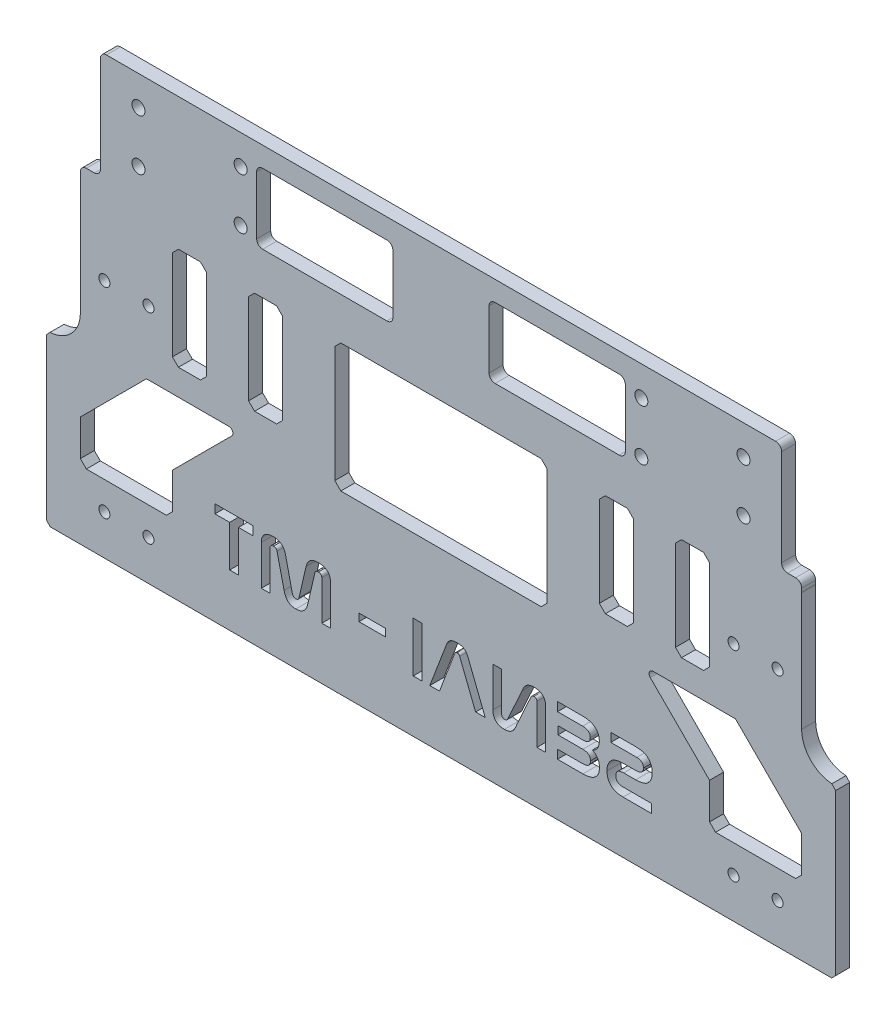
SolidWorks part; units mm, degrees
material "Liga 1060"
ref_plane "Plano frontal" through (0, 0, 0) normal (0, 0, 1) x (1, 0, 0)
ref_plane "Plano superior" through (0, 0, 0) normal (0, 1, 0) x (1, 0, 0)
ref_plane "Plano direito" through (0, 0, 0) normal (1, 0, 0) x (0, 0, -1)
sketch "Esboço1" plane through (0, 0, 0) normal (0, 0, 1) x (1, 0, 0)
  line L30 (-10, 125) -> (-10, 173)
  line L31 (-13, 176) -> (-347, 176)
  line L32 (-350, 173) -> (-350, 125)
  line L33 (-353, 122) -> (-357, 122)
  line L34 (-360, 119) -> (-360, 58)
  line L35 (-375.1111, 42.0247) -> (-377, 40.0278)
  line L36 (-377, 40.0278) -> (-377, -40)
  line L37 (-377, -40) -> (-375, -42)
  line L38 (-375, -42) -> (15, -42)
  line L39 (15, -42) -> (17, -40)
  line L40 (17, -40) -> (17, 40.0278)
  line L41 (17, 40.0278) -> (15.1111, 42.0247)
  line L42 (0, 58) -> (0, 117)
  line L43 (0, 117.2828) -> (0, 119)
  line L44 (-3, 122) -> (-7, 122)
  arc A20 (-10, 173) -> (-13, 176) centre (-13, 173) ccw
  arc A21 (-347, 176) -> (-350, 173) centre (-347, 173) ccw
  arc A22 (-353, 122) -> (-350, 125) centre (-353, 125) ccw
  arc A23 (-357, 122) -> (-360, 119) centre (-357, 119) ccw
  arc A24 (-375.1111, 42.0247) -> (-360, 58) centre (-376, 58) ccw
  arc A25 (0, 58) -> (15.1111, 42.0247) centre (16, 58) ccw
  arc A26 (0, 117) -> (-0.0295, 117.4199) centre (-3, 117) ccw
  arc A27 (0, 117.2828) -> (-0.0295, 117.4199) centre (-3.3115, 116.6414) ccw
  arc A28 (0, 119) -> (-3, 122) centre (-3, 119) ccw
  arc A29 (-10, 125) -> (-7, 122) centre (-7, 125) ccw
extrude "Ressalto-extrusão1" add sketch "Esboço1" along normal blind 6 contours L31 A21 L32 A22 L33 A23 L34 A24 L35 L36 L37 L38 L39 L40 L41 A25 L42 A26 A27 L43 A28 L44 A29 L30 A20
sketch "Esboço2" plane through (0, 0, 6) normal (0, 0, 1) x (1, 0, 0)
  line L0 (-180, 176) -> (-180, -42) construction
  line L1 (-13, 176) -> (-347, 176) construction
  line L2 (-375, -42) -> (15, -42) construction
  line L3 (-350, 173) -> (-350, 125) construction
  line L4 (-272, 166) -> (-204, 166)
  line L5 (-272, 166) -> (-272, 131)
  line L6 (-272, 131) -> (-204, 131)
  line L7 (-204, 166) -> (-204, 131)
  line L8 (-331, 161.2) -> (-280, 161.2) construction
  line L9 (-331, 161.2) -> (-331, 135.8) construction
  line L10 (-331, 135.8) -> (-280, 135.8) construction
  line L11 (-280, 161.2) -> (-280, 135.8) construction
  line L12 (-280, 148.5) -> (-272, 148.5) construction
  line L13 (-80, 148.5) -> (-88, 148.5) construction
  line L14 (-80, 161.2) -> (-80, 135.8) construction
  line L15 (-29, 135.8) -> (-80, 135.8) construction
  line L16 (-29, 161.2) -> (-29, 135.8) construction
  line L17 (-29, 161.2) -> (-80, 161.2) construction
  line L18 (-156, 166) -> (-156, 131)
  line L19 (-88, 131) -> (-156, 131)
  line L20 (-88, 166) -> (-88, 131)
  line L21 (-88, 166) -> (-156, 166)
  circle A0 centre (-331, 161.2) radius 3.25
  circle A1 centre (-280, 161.2) radius 3.25
  circle A2 centre (-331, 135.8) radius 3.25
  circle A3 centre (-280, 135.8) radius 3.25
  circle A4 centre (-80, 135.8) radius 3.25
  circle A5 centre (-29, 135.8) radius 3.25
  circle A6 centre (-80, 161.2) radius 3.25
  circle A7 centre (-29, 161.2) radius 3.25
  dimension "D3" = 25.4
  dimension "D5" = 6.5
  dimension "D1" = 51
  dimension "D2" = 68
  dimension "D4" = 35
  dimension "D6" = 8
  dimension "D7" = 10
  dimension "D8" = 78
extrude "Corte-extrusão1" cut sketch "Esboço2" against normal blind 6
fillet "Filete1" radius 3 8 edges at (-88, 131, 3) (-88, 166, 3) (-156, 166, 3) (-156, 131, 3) (-272, 131, 3) (-204, 131, 3) (-204, 166, 3) (-272, 166, 3)
sketch "Esboço3" plane through (0, 0, 0) normal (0, 0, -1) x (-1, 0, 0)
  line L0 (375, -42) -> (-15, -42) construction
  line L1 (12, 78) -> (34, 78) construction
  line L2 (12, 78) -> (12, -22) construction
  line L3 (12, -22) -> (34, -22) construction
  line L4 (34, 78) -> (34, -22) construction
  line L5 (180, 176) -> (180, -42) construction
  line L6 (13, 176) -> (347, 176) construction
  line L7 (326, 78) -> (326, -22) construction
  line L8 (348, -22) -> (326, -22) construction
  line L9 (348, 78) -> (348, -22) construction
  line L10 (348, 78) -> (326, 78) construction
  circle A0 centre (12, 78) radius 2.75
  circle A1 centre (34, 78) radius 2.75
  circle A2 centre (12, -22) radius 2.75
  circle A3 centre (34, -22) radius 2.75
  circle A4 centre (326, -22) radius 2.75
  circle A5 centre (348, -22) radius 2.75
  circle A6 centre (326, 78) radius 2.75
  circle A7 centre (348, 78) radius 2.75
  dimension "D5" = 5.5
  dimension "D6" = 5.5
  dimension "D1" = 22
  dimension "D2" = 100
  dimension "D3" = 20
  dimension "D4" = 146
extrude "Corte-extrusão2" cut sketch "Esboço3" against normal through all
sketch "Esboço4" plane through (0, 0, 0) normal (0, 0, -1) x (-1, 0, 0)
  line L8 (127, 110) -> (233, 110)
  line L9 (127, 110) -> (127, 46)
  line L10 (233, 110) -> (233, 46)
  line L11 (127, 46) -> (233, 46)
  line L26 (180, 110) -> (180, 176) construction
  line L27 (13, 176) -> (347, 176) construction
  line L28 (153, 131) -> (91, 131) construction
  dimension "D1" = 21
  dimension "D2" = 106
  dimension "D3" = 64
extrude "Corte-extrusão3" cut sketch "Esboço4" against normal through all
sketch "Esboço6" plane through (0, 0, 6) normal (0, 0, 1) x (1, 0, 0)
  text T0 " canintech" font "Neuropolitical Rg" height 26
extrude "Corte-extrusão4" cut sketch "Esboço6" against normal through all
sketch "Esboço7" plane through (0, 0, 6) normal (0, 0, 1) x (1, 0, 0)
  line L10 (-248.1953, 1.4651) -> (-242.6122, 1.4651)
  line L11 (-242.6137, 0.1618) -> (-242.6082, 5.1384) construction
  line L12 (-252.0392, -3.858) -> (-243.1564, -3.858)
  line L13 (-252.0392, -3.858) -> (-252.0392, 1.4637)
  line L14 (-262.9825, 1.4596) -> (-248.1953, 1.4651) construction
  line L15 (-252.0392, 1.4637) -> (-248.1953, 1.4651)
  line L16 (-242.6122, 1.4651) -> (-242.6122, -3.858)
  line L17 (-242.6122, -3.858) -> (-243.1564, -3.858)
  spline S0 degree 3 poles (-251.9587, -7.6854) (-251.529, -7.6843) (-250.7044, -7.6821) (-249.5179, -7.6097) (-248.4335, -7.4883) (-247.4508, -7.3043) (-246.5724, -7.0585) (-245.7969, -6.7579) (-245.1214, -6.4027) (-244.5487, -5.9757) (-244.0577, -5.483) (-243.6518, -4.9061) (-243.3004, -4.2586) (-243.0287, -3.5244) (-242.8221, -2.7132) (-242.68, -1.8243) (-242.6116, -0.8566) (-242.613, -0.1865) (-242.6137, 0.1618) knots 0 0 0 0 0.089644 0.172025 0.247884 0.317196 0.380397 0.437928 0.490462 0.539112 0.586442 0.63495 0.685774 0.739761 0.797833 0.860209 0.927326 1 1 1 1 construction
extrude "Ressalto-extrusão3" add sketch "Esboço7" against normal through all
chamfer "Chanfro1" distance 3 angle 45 4 edges at (-233, 110, 3) (-127, 110, 3) (-127, 46, 3) (-233, 46, 3)
sketch "Esboço8" plane through (0, 0, 6) normal (0, 0, 1) x (1, 0, 0)
  line L0 (-123.9584, 4.2367) -> (-123.9584, 0.7613)
  line L1 (-139.488, 0.7613) -> (-118.3713, 0.7613) construction
  line L2 (-123.9584, 0.7613) -> (-139.488, 0.7613)
  line L3 (-139.488, 0.7613) -> (-139.488, 4.2367)
  line L4 (-139.488, 4.2367) -> (-123.9584, 4.2367)
extrude "Ressalto-extrusão4" add sketch "Esboço8" against normal through all
sketch "Esboço9" plane through (0, 0, 6) normal (0, 0, 1) x (1, 0, 0)
  line L0 (-123.9584, 0.7613) -> (-123.9584, 4.2367)
  line L1 (-123.9584, 0.7613) -> (-128.9584, 0.7613)
  line L2 (-123.9584, 4.2367) -> (-128.9584, 4.2367)
  line L3 (-128.9584, 0.7613) -> (-128.9584, 4.2367)
  dimension "D1" = 5
extrude "Corte-extrusão5" cut sketch "Esboço9" against normal through all
sketch "Esboço10" plane through (0, 0, 6) normal (0, 0, 1) x (1, 0, 0)
  line L0 (-360, 13) -> (-360, -8)
  line L1 (-360, -8) -> (-314.0427, -8)
  line L2 (-314.0427, -8) -> (-314.0427, 13)
  line L3 (-281.0427, 46) -> (-259.0427, 46)
  line L4 (-259.0427, 46) -> (-259.0427, 110)
  line L5 (-259.0427, 110) -> (-314.0427, 110)
  line L6 (-314.0427, 110) -> (-314.0427, 58.9573)
  line L7 (-360, 13) -> (-314.0427, 58.9573)
  line L8 (-360, 119) -> (-360, 58) construction
  line L9 (-233, 49) -> (-233, 107) construction
  line L10 (-314.0427, 13) -> (-281.0427, 46)
  line L11 (-230, 110) -> (-130, 110) construction
  line L12 (-130, 46) -> (-230, 46) construction
  line L16 (-375, -42) -> (15, -42) construction
  line L17 (-180, 110) -> (-180, 46) construction
  line L18 (-45.9573, -8) -> (-45.9573, 13)
  line L19 (0, -8) -> (-45.9573, -8)
  line L20 (0, 13) -> (0, -8)
  line L21 (0, 13) -> (-45.9573, 58.9573)
  line L22 (-45.9573, 110) -> (-45.9573, 58.9573)
  line L23 (-100.9573, 110) -> (-45.9573, 110)
  line L24 (-100.9573, 46) -> (-100.9573, 110)
  line L25 (-78.9573, 46) -> (-100.9573, 46)
  line L26 (-45.9573, 13) -> (-78.9573, 46)
  dimension "D1" = 26.0427
  dimension "D2" = 55
  dimension "D3" = 135
  dimension "D4" = 34
  dimension "D5" = 21
  dimension "D6" = 21
extrude "Corte-extrusão6" cut sketch "Esboço10" against normal through all
sketch "Esboço11" plane through (0, 0, 6) normal (0, 0, 1) x (1, 0, 0)
  line L0 (-281.0427, 46) -> (-327, 46)
  line L1 (-314.0427, 58.9573) -> (-360, 13) construction
  line L2 (-314.0427, 58.9573) -> (-327, 46)
  line L3 (-314.0427, 58.9573) -> (-259.0427, 58.9573)
  line L4 (-259.0427, 46) -> (-259.0427, 110) construction
  line L5 (-259.0427, 58.9573) -> (-259.0427, 46)
  line L6 (-259.0427, 46) -> (-281.0427, 46)
  line L7 (-100.9573, 46) -> (-33, 46)
  line L8 (0, 13) -> (-45.9573, 58.9573) construction
  line L9 (-33, 46) -> (-45.9573, 58.9573)
  line L10 (-45.9573, 58.9573) -> (-100.9573, 58.9573)
  line L11 (-100.9573, 110) -> (-100.9573, 46) construction
  line L12 (-100.9573, 58.9573) -> (-100.9573, 46)
extrude "Ressalto-extrusão5" add sketch "Esboço11" against normal through all contours L10 L12 L7 L9 | L6 L0 L2 L3 L5
sketch "Esboço12" plane through (0, 0, 6) normal (0, 0, 1) x (1, 0, 0)
  line L0 (-297.0427, 110) -> (-297.0427, 58.9573)
  line L1 (-297.0427, 110) -> (-276.0427, 110)
  line L2 (-297.0427, 58.9573) -> (-276.0427, 58.9573)
  line L3 (-276.0427, 110) -> (-276.0427, 58.9573)
  line L4 (-259.0427, 110) -> (-314.0427, 110) construction
  line L5 (-314.0427, 58.9573) -> (-259.0427, 58.9573) construction
  line L6 (-62.9573, 110) -> (-62.9573, 58.9573)
  line L7 (-62.9573, 110) -> (-83.9573, 110)
  line L8 (-62.9573, 58.9573) -> (-83.9573, 58.9573)
  line L9 (-83.9573, 110) -> (-83.9573, 58.9573)
  line L10 (-45.9573, 110) -> (-100.9573, 110) construction
  line L11 (-45.9573, 58.9573) -> (-100.9573, 58.9573) construction
  line L13 (-276.0427, 110) -> (-259.0427, 110) construction
  line L14 (-297.0427, 110) -> (-314.0427, 110) construction
  line L15 (-83.9573, 110) -> (-100.9573, 110) construction
  line L16 (-62.9573, 110) -> (-45.9573, 110) construction
  dimension "D1" = 21
  dimension "D2" = 21
extrude "Ressalto-extrusão6" add sketch "Esboço12" against normal through all
chamfer "Chanfro3" distance 3 angle 45 20 edges at (0, -8, 3) (-45.9573, -8, 3) (-314.0427, -8, 3) (-360, -8, 3) (-62.9573, 58.9573, 2.9927) (-45.9573, 58.9573, 3) (-83.9573, 58.9573, 2.9927) (-100.9573, 58.9573, 3) (-62.9573, 110, 3) (-100.9573, 110, 3) (-83.9573, 110, 3) (-45.9573, 110, 3) (-259.0427, 110, 3) (-297.0427, 110, 3) (-314.0427, 110, 3) (-276.0427, 110, 3) (-259.0427, 58.9573, 3) (-297.0427, 58.9573, 2.9927) (-276.0427, 58.9573, 2.9927) (-314.0427, 58.9573, 3)
sketch "Esboço13" plane through (0, 0, 6) normal (0, 0, 1) x (1, 0, 0)
  text T0 "SENAI MT - SINOP - BRASIL" font "Neuropolitical Rg" height 10
extrude "Corte-extrusão7" cut sketch "Esboço13" against normal through all
sketch "Esboço14" plane through (0, 0, 6) normal (0, 0, 1) x (1, 0, 0)
  line L0 (-258.8839, -26.4965) -> (-259.9219, -28.2139)
  line L1 (-259.9219, -28.2139) -> (-253.0215, -28.2139)
  line L2 (-253.0215, -28.2139) -> (-254.0594, -26.4965)
  line L3 (-254.0594, -26.4965) -> (-258.8839, -26.4965)
  line L25 (-147.8817, -25.9424) -> (-147.8817, -27.6852)
  line L26 (-147.8817, -25.9424) -> (-144.8817, -25.9424)
  line L29 (-147.8817, -27.6852) -> (-144.8817, -27.6852)
  line L65 (-144.8817, -25.9424) -> (-144.8817, -27.6852)
  line L68 (-158.9663, -22.3954) -> (-158.9663, -20.4568)
  line L70 (-158.9663, -22.3954) -> (-158.9663, -22.5502)
  line L71 (-158.9663, -22.5502) -> (-155.9663, -22.5502)
  line L72 (-155.9663, -22.3954) -> (-155.9663, -22.5502)
  line L73 (-158.9663, -20.4568) -> (-155.9663, -20.4568)
  line L74 (-155.9663, -20.4568) -> (-155.9663, -22.5502)
  line L75 (-88.867, -26.4965) -> (-84.0425, -26.4965)
  line L76 (-158.9663, -28.1647) -> (-155.9663, -28.1647)
  line L77 (-158.9663, -28.1647) -> (-158.9663, -31.247)
  line L78 (-158.9663, -31.247) -> (-155.9663, -31.247)
  line L79 (-155.9663, -28.1647) -> (-155.9663, -31.247)
  line L80 (-84.0425, -26.4965) -> (-83.0045, -28.2139)
  line L81 (-83.0045, -28.2139) -> (-89.905, -28.2139)
  line L82 (-89.905, -28.2139) -> (-88.867, -26.4965)
  line L83 (-98.7298, -25.5363) -> (-104.2945, -25.5363) construction
  line L84 (-98.4573, -25.5363) -> (-104.2945, -25.5363)
  line L85 (-98.4573, -25.5363) -> (-98.4573, -27.1437)
  line L86 (-98.4573, -27.1437) -> (-104.2945, -27.1437)
  line L87 (-104.2945, -25.5363) -> (-104.2945, -27.1437)
  line L88 (-104.2945, -30.5278) -> (-104.2945, -26.9061) construction
  line L89 (-100.3996, -27.1437) -> (-98.6088, -27.1437) construction
  line L90 (-111.1748, -20.5405) -> (-119.5737, -20.5385) construction
  line L91 (-115.3743, -20.5395) -> (-112.6341, -20.5395)
  line L92 (-115.3743, -20.5395) -> (-115.3743, -22.3952)
  line L93 (-115.3743, -22.3952) -> (-112.6341, -22.3952)
  line L94 (-112.6341, -20.5395) -> (-112.6341, -22.3952)
  line L95 (-117.4248, -22.3952) -> (-111.3517, -22.3952) construction
  line L96 (-111.1452, -28.6623) -> (-117.4248, -28.6604) construction
  line L97 (-115.3002, -28.661) -> (-112.6341, -28.661)
  line L98 (-115.3002, -28.661) -> (-115.3002, -30.5171)
  line L99 (-115.3002, -30.5171) -> (-112.6341, -30.5171)
  line L100 (-112.6341, -28.661) -> (-112.6341, -30.5171)
  line L101 (-119.5737, -30.5171) -> (-111.0266, -30.5171) construction
  dimension "D1" = 3
  dimension "D2" = 3
extrude "Ressalto-extrusão8" add sketch "Esboço14" against normal through all
fillet "Filete2" radius 2 2 edges at (-281.0427, 46, 3) (-78.9573, 46, 3)
sketch "Esboço15" plane through (0, 0, 6) normal (0, 0, 1) x (1, 0, 0)
  line L0 (-305.1197, 14.02) -> (-201.8576, 26.6471)
  line L1 (-201.8576, 26.6471) -> (-69.1323, 24.9635)
  line L2 (-69.1323, 24.9635) -> (-54.2603, 12.0557)
  line L3 (-54.2603, 12.0557) -> (-48.46, -35.3775)
  line L4 (-48.46, -35.3775) -> (-307.6451, -35.3775)
  line L5 (-307.6451, -35.3775) -> (-305.1197, 14.02)
extrude "Ressalto-extrusão9" add sketch "Esboço15" against normal through all contours L5 L4 L3 L2 L1 L0
sketch "Esboço16" plane through (0, 0, 0) normal (0, 0, 1) x (1, 0, 0)
  line L15 (-13, 176) -> (-347, 176)
  line L16 (-350, 173) -> (-350, 125)
  line L17 (-353, 122) -> (-357, 122)
  line L18 (-360, 119) -> (-360, 58)
  line L19 (-375.1111, 42.0247) -> (-377, 40.0278)
  line L20 (-377, 40.0278) -> (-377, -40)
  line L21 (-377, -40) -> (-375, -42)
  line L22 (-375, -42) -> (15, -42)
  line L23 (15, -42) -> (17, -40)
  line L24 (17, -40) -> (17, 40.0278)
  line L25 (17, 40.0278) -> (15.1111, 42.0247)
  line L26 (0, 58) -> (0, 117)
  line L27 (0, 117.2828) -> (0, 119)
  line L28 (-3, 122) -> (-7, 122)
  line L29 (-10, 125) -> (-10, 173)
  line L30 (-13, 176) -> (-347, 176)
  line L31 (-350, 173) -> (-350, 125)
  line L32 (-353, 122) -> (-357, 122)
  line L33 (-360, 119) -> (-360, 58)
  line L34 (-375.1111, 42.0247) -> (-377, 40.0278)
  line L35 (-377, 40.0278) -> (-377, -40)
  line L36 (-377, -40) -> (-375, -42)
  line L37 (-375, -42) -> (15, -42)
  line L38 (15, -42) -> (17, -40)
  line L39 (17, -40) -> (17, 40.0278)
  line L40 (17, 40.0278) -> (15.1111, 42.0247)
  line L41 (0, 58) -> (0, 117)
  line L42 (0, 117.2828) -> (0, 119)
  line L43 (-3, 122) -> (-7, 122)
  line L44 (-10, 125) -> (-10, 173)
  arc A10 (-10, 173) -> (-13, 176) centre (-13, 173) ccw
  arc A11 (-347, 176) -> (-350, 173) centre (-347, 173) ccw
  arc A12 (-353, 122) -> (-350, 125) centre (-353, 125) ccw
  arc A13 (-357, 122) -> (-360, 119) centre (-357, 119) ccw
  arc A14 (-375.1111, 42.0247) -> (-360, 58) centre (-376, 58) ccw
  arc A15 (0, 58) -> (15.1111, 42.0247) centre (16, 58) ccw
  arc A16 (0, 117) -> (-0.0295, 117.4199) centre (-3, 117) ccw
  arc A17 (0, 117.2828) -> (-0.0295, 117.4199) centre (-3.3115, 116.6414) ccw
  arc A18 (0, 119) -> (-3, 122) centre (-3, 119) ccw
  arc A19 (-10, 125) -> (-7, 122) centre (-7, 125) ccw
  arc A20 (-10, 173) -> (-13, 176) centre (-13, 173) ccw
  arc A21 (-347, 176) -> (-350, 173) centre (-347, 173) ccw
  arc A22 (-353, 122) -> (-350, 125) centre (-353, 125) ccw
  arc A23 (-357, 122) -> (-360, 119) centre (-357, 119) ccw
  arc A24 (-375.1111, 42.0247) -> (-360, 58) centre (-376, 58) ccw
  arc A25 (0, 58) -> (15.1111, 42.0247) centre (16, 58) ccw
  arc A26 (0, 117) -> (-0.0295, 117.4199) centre (-3, 117) ccw
  arc A27 (0, 117.2828) -> (-0.0295, 117.4199) centre (-3.3115, 116.6414) ccw
  arc A28 (0, 119) -> (-3, 122) centre (-3, 119) ccw
  arc A29 (-10, 125) -> (-7, 122) centre (-7, 125) ccw
  dimension "D1" = 0
extrude "Ressalto-extrusão10" add sketch "Esboço16" against normal blind 1
sketch "Esboço17" plane through (0, 0, 0) normal (0, 0, 1) x (1, 0, 0)
  line L0 (0, 13) -> (-33, 46) construction
  line L1 (-33, 46) -> (-74.1288, 46) construction
  line L2 (-75.5431, 42.5858) -> (-45.9573, 13) construction
  line L3 (-45.9573, 13) -> (-45.9573, -5) construction
  line L4 (-45.9573, -5) -> (-42.9573, -8) construction
  line L5 (-42.9573, -8) -> (-3, -8) construction
  line L6 (-3, -8) -> (0, -5) construction
  line L7 (0, -5) -> (0, 13) construction
  line L8 (-285.8712, 46) -> (-327, 46) construction
  line L9 (-327, 46) -> (-360, 13) construction
  line L10 (-360, 13) -> (-360, -5) construction
  line L11 (-360, -5) -> (-357, -8) construction
  line L12 (-357, -8) -> (-317.0427, -8) construction
  line L13 (-317.0427, -8) -> (-314.0427, -5) construction
  line L14 (-314.0427, -5) -> (-314.0427, 13) construction
  line L15 (-314.0427, 13) -> (-284.4569, 42.5858) construction
  line L16 (-273.0427, 58.9573) -> (-262.0427, 58.9573) construction
  line L17 (-262.0427, 58.9573) -> (-259.0427, 61.9573) construction
  line L18 (-259.0427, 61.9573) -> (-259.0427, 107) construction
  line L19 (-259.0427, 107) -> (-262.0427, 110) construction
  line L20 (-262.0427, 110) -> (-273.0427, 110) construction
  line L21 (-273.0427, 110) -> (-276.0427, 107) construction
  line L22 (-276.0427, 107) -> (-276.0427, 61.9573) construction
  line L23 (-276.0427, 61.9573) -> (-273.0427, 58.9573) construction
  line L24 (-311.0427, 58.9573) -> (-300.0427, 58.9573) construction
  line L25 (-300.0427, 58.9573) -> (-297.0427, 61.9573) construction
  line L26 (-297.0427, 61.9573) -> (-297.0427, 107) construction
  line L27 (-297.0427, 107) -> (-300.0427, 110) construction
  line L28 (-300.0427, 110) -> (-311.0427, 110) construction
  line L29 (-311.0427, 110) -> (-314.0427, 107) construction
  line L30 (-314.0427, 107) -> (-314.0427, 61.9573) construction
  line L31 (-314.0427, 61.9573) -> (-311.0427, 58.9573) construction
  line L32 (-127, 107) -> (-130, 110) construction
  line L33 (-130, 110) -> (-230, 110) construction
  line L34 (-230, 110) -> (-233, 107) construction
  line L35 (-233, 107) -> (-233, 49) construction
  line L36 (-233, 49) -> (-230, 46) construction
  line L37 (-230, 46) -> (-130, 46) construction
  line L38 (-130, 46) -> (-127, 49) construction
  line L39 (-127, 49) -> (-127, 107) construction
  line L40 (-100.9573, 61.9573) -> (-97.9573, 58.9573) construction
  line L41 (-97.9573, 58.9573) -> (-86.9573, 58.9573) construction
  line L42 (-86.9573, 58.9573) -> (-83.9573, 61.9573) construction
  line L43 (-83.9573, 61.9573) -> (-83.9573, 107) construction
  line L44 (-83.9573, 107) -> (-86.9573, 110) construction
  line L45 (-86.9573, 110) -> (-97.9573, 110) construction
  line L46 (-97.9573, 110) -> (-100.9573, 107) construction
  line L47 (-100.9573, 107) -> (-100.9573, 61.9573) construction
  line L48 (-62.9573, 61.9573) -> (-59.9573, 58.9573) construction
  line L49 (-59.9573, 58.9573) -> (-48.9573, 58.9573) construction
  line L50 (-48.9573, 58.9573) -> (-45.9573, 61.9573) construction
  line L51 (-45.9573, 61.9573) -> (-45.9573, 107) construction
  line L52 (-45.9573, 107) -> (-48.9573, 110) construction
  line L53 (-48.9573, 110) -> (-59.9573, 110) construction
  line L54 (-59.9573, 110) -> (-62.9573, 107) construction
  line L55 (-62.9573, 107) -> (-62.9573, 61.9573) construction
  line L56 (-91, 166) -> (-153, 166) construction
  line L57 (-156, 163) -> (-156, 134) construction
  line L58 (-153, 131) -> (-91, 131) construction
  line L59 (-88, 134) -> (-88, 163) construction
  line L60 (-204, 134) -> (-204, 163) construction
  line L61 (-207, 166) -> (-269, 166) construction
  line L62 (-272, 163) -> (-272, 134) construction
  line L63 (-269, 131) -> (-207, 131) construction
  line L64 (0, 13) -> (-33, 46)
  line L65 (-33, 46) -> (-74.1288, 46)
  line L66 (-75.5431, 42.5858) -> (-45.9573, 13)
  line L67 (-45.9573, 13) -> (-45.9573, -5)
  line L68 (-45.9573, -5) -> (-42.9573, -8)
  line L69 (-42.9573, -8) -> (-3, -8)
  line L70 (-3, -8) -> (0, -5)
  line L71 (0, -5) -> (0, 13)
  line L72 (-285.8712, 46) -> (-327, 46)
  line L73 (-327, 46) -> (-360, 13)
  line L74 (-360, 13) -> (-360, -5)
  line L75 (-360, -5) -> (-357, -8)
  line L76 (-357, -8) -> (-317.0427, -8)
  line L77 (-317.0427, -8) -> (-314.0427, -5)
  line L78 (-314.0427, -5) -> (-314.0427, 13)
  line L79 (-314.0427, 13) -> (-284.4569, 42.5858)
  line L80 (-273.0427, 58.9573) -> (-262.0427, 58.9573)
  line L81 (-262.0427, 58.9573) -> (-259.0427, 61.9573)
  line L82 (-259.0427, 61.9573) -> (-259.0427, 107)
  line L83 (-259.0427, 107) -> (-262.0427, 110)
  line L84 (-262.0427, 110) -> (-273.0427, 110)
  line L85 (-273.0427, 110) -> (-276.0427, 107)
  line L86 (-276.0427, 107) -> (-276.0427, 61.9573)
  line L87 (-276.0427, 61.9573) -> (-273.0427, 58.9573)
  line L88 (-311.0427, 58.9573) -> (-300.0427, 58.9573)
  line L89 (-300.0427, 58.9573) -> (-297.0427, 61.9573)
  line L90 (-297.0427, 61.9573) -> (-297.0427, 107)
  line L91 (-297.0427, 107) -> (-300.0427, 110)
  line L92 (-300.0427, 110) -> (-311.0427, 110)
  line L93 (-311.0427, 110) -> (-314.0427, 107)
  line L94 (-314.0427, 107) -> (-314.0427, 61.9573)
  line L95 (-314.0427, 61.9573) -> (-311.0427, 58.9573)
  line L96 (-127, 107) -> (-130, 110)
  line L97 (-130, 110) -> (-230, 110)
  line L98 (-230, 110) -> (-233, 107)
  line L99 (-233, 107) -> (-233, 49)
  line L100 (-233, 49) -> (-230, 46)
  line L101 (-230, 46) -> (-130, 46)
  line L102 (-130, 46) -> (-127, 49)
  line L103 (-127, 49) -> (-127, 107)
  line L104 (-100.9573, 61.9573) -> (-97.9573, 58.9573)
  line L105 (-97.9573, 58.9573) -> (-86.9573, 58.9573)
  line L106 (-86.9573, 58.9573) -> (-83.9573, 61.9573)
  line L107 (-83.9573, 61.9573) -> (-83.9573, 107)
  line L108 (-83.9573, 107) -> (-86.9573, 110)
  line L109 (-86.9573, 110) -> (-97.9573, 110)
  line L110 (-97.9573, 110) -> (-100.9573, 107)
  line L111 (-100.9573, 107) -> (-100.9573, 61.9573)
  line L112 (-62.9573, 61.9573) -> (-59.9573, 58.9573)
  line L113 (-59.9573, 58.9573) -> (-48.9573, 58.9573)
  line L114 (-48.9573, 58.9573) -> (-45.9573, 61.9573)
  line L115 (-45.9573, 61.9573) -> (-45.9573, 107)
  line L116 (-45.9573, 107) -> (-48.9573, 110)
  line L117 (-48.9573, 110) -> (-59.9573, 110)
  line L118 (-59.9573, 110) -> (-62.9573, 107)
  line L119 (-62.9573, 107) -> (-62.9573, 61.9573)
  line L120 (-91, 166) -> (-153, 166)
  line L121 (-156, 163) -> (-156, 134)
  line L122 (-153, 131) -> (-91, 131)
  line L123 (-88, 134) -> (-88, 163)
  line L124 (-204, 134) -> (-204, 163)
  line L125 (-207, 166) -> (-269, 166)
  line L126 (-272, 163) -> (-272, 134)
  line L127 (-269, 131) -> (-207, 131)
  circle A0 centre (-12, -22) radius 2.75 construction
  circle A1 centre (-34, -22) radius 2.75 construction
  circle A2 centre (-12, 78) radius 2.75 construction
  circle A3 centre (-34, 78) radius 2.75 construction
  arc A4 (-74.1288, 46) -> (-75.5431, 42.5858) centre (-74.1288, 44) ccw construction
  circle A5 centre (-326, -22) radius 2.75 construction
  circle A6 centre (-348, -22) radius 2.75 construction
  arc A7 (-284.4569, 42.5858) -> (-285.8712, 46) centre (-285.8712, 44) ccw construction
  circle A8 centre (-326, 78) radius 2.75 construction
  circle A9 centre (-348, 78) radius 2.75 construction
  circle A10 centre (-280, 135.8) radius 3.25 construction
  circle A11 centre (-280, 161.2) radius 3.25 construction
  circle A12 centre (-331, 135.8) radius 3.25 construction
  circle A13 centre (-331, 161.2) radius 3.25 construction
  circle A14 centre (-80, 135.8) radius 3.25 construction
  circle A15 centre (-29, 135.8) radius 3.25 construction
  circle A16 centre (-29, 161.2) radius 3.25 construction
  circle A17 centre (-80, 161.2) radius 3.25 construction
  arc A18 (-88, 163) -> (-91, 166) centre (-91, 163) ccw construction
  arc A19 (-153, 166) -> (-156, 163) centre (-153, 163) ccw construction
  arc A20 (-156, 134) -> (-153, 131) centre (-153, 134) ccw construction
  arc A21 (-91, 131) -> (-88, 134) centre (-91, 134) ccw construction
  arc A22 (-207, 131) -> (-204, 134) centre (-207, 134) ccw construction
  arc A23 (-204, 163) -> (-207, 166) centre (-207, 163) ccw construction
  arc A24 (-269, 166) -> (-272, 163) centre (-269, 163) ccw construction
  arc A25 (-272, 134) -> (-269, 131) centre (-269, 134) ccw construction
  circle A26 centre (-12, -22) radius 2.75
  circle A27 centre (-34, -22) radius 2.75
  circle A28 centre (-12, 78) radius 2.75
  circle A29 centre (-34, 78) radius 2.75
  arc A30 (-74.1288, 46) -> (-75.5431, 42.5858) centre (-74.1288, 44) ccw
  circle A31 centre (-326, -22) radius 2.75
  circle A32 centre (-348, -22) radius 2.75
  arc A33 (-284.4569, 42.5858) -> (-285.8712, 46) centre (-285.8712, 44) ccw
  circle A34 centre (-326, 78) radius 2.75
  circle A35 centre (-348, 78) radius 2.75
  circle A36 centre (-280, 135.8) radius 3.25
  circle A37 centre (-280, 161.2) radius 3.25
  circle A38 centre (-331, 135.8) radius 3.25
  circle A39 centre (-331, 161.2) radius 3.25
  circle A40 centre (-80, 135.8) radius 3.25
  circle A41 centre (-29, 135.8) radius 3.25
  circle A42 centre (-29, 161.2) radius 3.25
  circle A43 centre (-80, 161.2) radius 3.25
  arc A44 (-88, 163) -> (-91, 166) centre (-91, 163) ccw
  arc A45 (-153, 166) -> (-156, 163) centre (-153, 163) ccw
  arc A46 (-156, 134) -> (-153, 131) centre (-153, 134) ccw
  arc A47 (-91, 131) -> (-88, 134) centre (-91, 134) ccw
  arc A48 (-207, 131) -> (-204, 134) centre (-207, 134) ccw
  arc A49 (-204, 163) -> (-207, 166) centre (-207, 163) ccw
  arc A50 (-269, 166) -> (-272, 163) centre (-269, 163) ccw
  arc A51 (-272, 134) -> (-269, 131) centre (-269, 134) ccw
extrude "Corte-extrusão8" cut sketch "Esboço17" against normal through all
sketch "Esboço19" plane through (0, 0, -1) normal (0, 0, -1) x (-1, 0, 0)
  text T0 "SENAI - MT" font "Nasalization Rg" height 25
extrude "Corte-extrusão10" cut sketch "Esboço19" against normal through all
